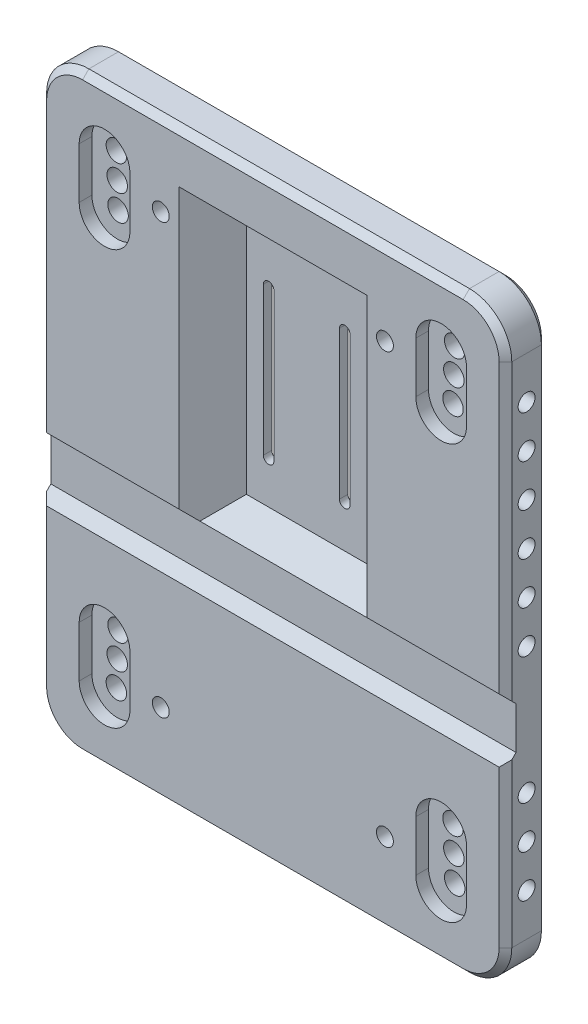
SolidWorks part; units mm, degrees
ref_plane "Front Plane" through (0, 0, 0) normal (0, 0, 1) x (1, 0, 0)
ref_plane "Top Plane" through (0, 0, 0) normal (0, 1, 0) x (1, 0, 0)
ref_plane "Right Plane" through (0, 0, 0) normal (1, 0, 0) x (0, 0, -1)
sketch "Sketch1" plane through (0, 0, 0) normal (0, 0, 1) x (1, 0, 0)
  line L0 (0, 39.3429) -> (0, -40.5174) construction
  line L1 (-55, 70) -> (55, 70)
  line L2 (-55, 70) -> (-55, -70)
  line L3 (-55, -70) -> (55, -70)
  line L4 (55, 70) -> (55, -70)
  line L5 (-55, 70) -> (55, -70) construction
  line L6 (-55, -70) -> (55, 70) construction
  line L7 (-36.7996, 0) -> (34.7101, 0) construction
  line L8 (-9, 40) -> (-9, 5) construction
  line L9 (-7.75, 40) -> (-7.75, 5)
  line L10 (-10.25, 40) -> (-10.25, 5)
  line L11 (9, 40) -> (9, 5) construction
  line L14 (7.75, 40) -> (7.75, 5)
  line L15 (10.25, 40) -> (10.25, 5)
  circle A0 centre (-26.5, 50.75) radius 2
  circle A1 centre (26.5, 50.75) radius 2
  circle A2 centre (26.5, -50.75) radius 2
  circle A3 centre (-26.5, -50.75) radius 2
  circle A4 centre (-40, 55) radius 2.425
  circle A5 centre (40, 55) radius 2.425
  circle A6 centre (40, -55) radius 2.425
  circle A7 centre (-40, -55) radius 2.425
  circle A8 centre (-39.8, 49) radius 2.425
  circle A9 centre (39.8, 49) radius 2.425
  circle A10 centre (39.8, -49) radius 2.425
  circle A11 centre (-39.8, -49) radius 2.425
  circle A12 centre (-39.6, 43.0033) radius 2.425
  circle A13 centre (39.6, 43.0033) radius 2.425
  circle A14 centre (39.6, -43.0033) radius 2.425
  circle A15 centre (-39.6, -43.0033) radius 2.425
  arc A16 (-7.75, 40) -> (-10.25, 40) centre (-9, 40) ccw
  arc A17 (-10.25, 5) -> (-7.75, 5) centre (-9, 5) ccw
  arc A20 (7.75, 40) -> (10.25, 40) centre (9, 40) cw
  arc A21 (10.25, 5) -> (7.75, 5) centre (9, 5) cw
  point P0 (0, 0)
  point P44 (-9, 22.5)
  point P51 (9, 22.5)
  dimension "D3" = 4
  dimension "D4" = 26.5
  dimension "D5" = 50.75
  dimension "D6" = 4.85
  dimension "D7" = 40
  dimension "D8" = 15
  dimension "D9" = 4.85
  dimension "D10" = 39.8
  dimension "D11" = 6
  dimension "D12" = 4.85
  dimension "D13" = 6
  dimension "D14" = 39.6
  dimension "D15" = 1.25
  dimension "D1" = 110
  dimension "D2" = 140
  dimension "D16" = 9
  dimension "D17" = 5
  dimension "D18" = 35
extrude "Boss-Extrude1" add sketch "Sketch1" along normal blind 10
fillet "Fillet1" radius 10 4 edges at (-55, -70, 5) (55, -70, 5) (-55, 70, 5) (55, 70, 5)
sketch "Sketch3" plane through (0, 0, 10) normal (0, 0, 1) x (1, 0, 0)
  line L0 (10.25, 5) -> (10.25, 40) construction
  line L1 (-14.25, 50) -> (14.25, 50)
  line L2 (-14.25, 50) -> (-14.25, -5)
  line L3 (-14.25, -5) -> (14.25, -5)
  line L4 (14.25, 50) -> (14.25, -5)
  line L5 (-14.25, 50) -> (14.25, -5) construction
  line L6 (-14.25, -5) -> (14.25, 50) construction
  arc A0 (-7.75, 40) -> (-10.25, 40) centre (-9, 40) ccw construction
  arc A1 (-10.25, 5) -> (-7.75, 5) centre (-9, 5) ccw construction
  point P0 (0, 22.5)
  dimension "D1" = 10
  dimension "D2" = 10
  dimension "D3" = 4
extrude "Cut-Extrude1" cut sketch "Sketch3" against normal blind 8
chamfer "Chamfer1" distance 8 angle 45 4 edges at (0, -5, 10) (14.25, 22.5, 10) (0, 50, 10) (-14.25, 22.5, 10)
sketch "Sketch5" plane through (-55, 0, 0) normal (-1, 0, 0) x (0, 0, 1)
  line L0 (10, 60) -> (0, 60) construction
  line L1 (10, 60) -> (10, -60) construction
  circle A0 centre (5, 50) radius 2
  circle A1 centre (5, 40) radius 2
  circle A2 centre (5, 30) radius 2
  circle A3 centre (5, 20) radius 2
  circle A4 centre (5, 10) radius 2
  circle A5 centre (5, 0) radius 2
  circle A6 centre (5, -10) radius 2
  circle A7 centre (5, -20) radius 2
  circle A8 centre (5, -30) radius 2
  circle A9 centre (5, -40) radius 2
  circle A10 centre (5, -50) radius 2
  dimension "D1" = 10
  dimension "D2" = 4
  dimension "D3" = 5
  dimension "D4" = 11
extrude "Cut-Extrude3" cut sketch "Sketch5" against normal blind 8
sketch "Sketch6" plane through (55, 0, 0) normal (1, 0, 0) x (0, 0, -1)
  line L0 (0, 60) -> (-10, 60) construction
  line L1 (0, -60) -> (0, 60) construction
  circle A0 centre (-5, 50) radius 2
  circle A1 centre (-5, 40) radius 2
  circle A2 centre (-5, 30) radius 2
  circle A3 centre (-5, 20) radius 2
  circle A4 centre (-5, 10) radius 2
  circle A5 centre (-5, 0) radius 2
  circle A6 centre (-5, -10) radius 2
  circle A7 centre (-5, -20) radius 2
  circle A8 centre (-5, -30) radius 2
  circle A9 centre (-5, -40) radius 2
  circle A10 centre (-5, -50) radius 2
  dimension "D1" = 4
  dimension "D2" = 10
  dimension "D3" = 5
  dimension "D4" = 11
extrude "Cut-Extrude4" cut sketch "Sketch6" against normal blind 8
sketch "Sketch7" plane through (0, 0, 10) normal (0, 0, 1) x (1, 0, 0)
  line L0 (-55, 60) -> (-55, -60) construction
  line L1 (-55, -23) -> (55, -23)
  line L2 (-55, -23) -> (-55, -8)
  line L3 (-55, -8) -> (55, -8)
  line L4 (55, -23) -> (55, -8)
  line L5 (55, -60) -> (55, 60) construction
  line L6 (45, 70) -> (-45, 70) construction
  dimension "D1" = 15
  dimension "D2" = 78
extrude "Cut-Extrude7" cut sketch "Sketch7" against normal blind 2.5
chamfer "Chamfer3" distance 2.5 angle 45 3 edges at (0, -23, 7.5) (-37.375, -8, 7.5) (37.375, -8, 7.5)
chamfer "Chamfer4" distance 1.5 angle 45 18 edges at (-55, 0, 0) (-52.0711, -67.0711, 0) (-52.0711, 67.0711, 0) (0, -70, 0) (0, 70, 0) (52.0711, -67.0711, 0) (52.0711, 67.0711, 0) (55, 0, 0) (55, 26, 10) (-55, 26, 10) (52.0711, 67.0711, 10) (-52.0711, 67.0711, 10) (0, 70, 10) (-55, -41.5, 10) (55, -41.5, 10) (-52.0711, -67.0711, 10) (52.0711, -67.0711, 10) (0, -70, 10)
sketch "Sketch8" plane through (0, 0, 10) normal (0, 0, -1) x (-1, 0, 0)
  line L0 (-39.8, 43) -> (-39.8, 55) construction
  line L1 (-45.8, 43) -> (-45.8, 55)
  line L2 (-33.8, 43) -> (-33.8, 55)
  line L3 (0, 50.6508) -> (0, -40.492) construction
  line L4 (-37.1333, 0) -> (41.9805, 0) construction
  line L5 (39.8, 43) -> (39.8, 55) construction
  line L6 (45.8, 43) -> (45.8, 55)
  line L7 (33.8, 43) -> (33.8, 55)
  line L8 (39.8, -43) -> (39.8, -55) construction
  line L9 (45.8, -43) -> (45.8, -55)
  line L10 (33.8, -43) -> (33.8, -55)
  line L11 (-39.8, -43) -> (-39.8, -55) construction
  line L12 (-45.8, -43) -> (-45.8, -55)
  line L13 (-33.8, -43) -> (-33.8, -55)
  arc A0 (-45.8, 43) -> (-33.8, 43) centre (-39.8, 43) ccw
  arc A1 (-33.8, 55) -> (-45.8, 55) centre (-39.8, 55) ccw
  circle A2 centre (-39.8, 49) radius 2.425 construction
  arc A3 (45.8, 43) -> (33.8, 43) centre (39.8, 43) cw
  arc A4 (33.8, 55) -> (45.8, 55) centre (39.8, 55) cw
  arc A5 (45.8, -43) -> (33.8, -43) centre (39.8, -43) ccw
  arc A6 (33.8, -55) -> (45.8, -55) centre (39.8, -55) ccw
  arc A7 (-45.8, -43) -> (-33.8, -43) centre (-39.8, -43) cw
  arc A8 (-33.8, -55) -> (-45.8, -55) centre (-39.8, -55) cw
  point P2 (-39.8, 49)
  point P7 (-39.6, 43.0033)
  point P10 (-40, 55)
  point P20 (39.8, 49)
  point P27 (39.8, -49)
  point P34 (-39.8, -49)
  dimension "D1" = 6
extrude "Cut-Extrude8" cut sketch "Sketch8" along normal blind 3
sketch "Sketch9" plane through (55, 0, 0) normal (1, 0, 0) x (0, 0, -1)
  line L0 (-7.4795, -9.1307) -> (-5.6879, -6.8273)
  line L1 (-5.6879, -6.8273) -> (-2.4538, -7.5718)
  line L2 (-2.4538, -7.5718) -> (-2.4538, -22.4394)
  line L3 (-2.4538, -22.4394) -> (-6.4325, -22.4394)
  line L4 (-6.4325, -22.4394) -> (-7.1506, -20.5769)
  line L5 (-7.1506, -20.5769) -> (-7.1506, -10.5035)
  line L6 (-7.1506, -10.5035) -> (-7.4795, -9.1307)
extrude "Boss-Extrude3" add sketch "Sketch9" against normal blind 10
sketch "Sketch10" plane through (0, 0, 0) normal (0, 0, -1) x (-1, 0, 0)
  line L0 (0, 41.7558) -> (0, -38.9553) construction
  line L1 (-29.95, 54.2) -> (-23.05, 54.2)
  line L2 (-29.95, 54.2) -> (-29.95, 47.3)
  line L3 (-29.95, 47.3) -> (-23.05, 47.3)
  line L4 (-23.05, 54.2) -> (-23.05, 47.3)
  line L5 (-29.95, 54.2) -> (-23.05, 47.3) construction
  line L6 (-29.95, 47.3) -> (-23.05, 54.2) construction
  line L7 (0, -38.9553) -> (0, 0) construction
  line L8 (0, 0) -> (24.8367, 0) construction
  line L9 (29.95, 47.3) -> (23.05, 47.3)
  line L10 (23.05, 54.2) -> (23.05, 47.3)
  line L11 (29.95, 54.2) -> (23.05, 54.2)
  line L12 (29.95, 54.2) -> (29.95, 47.3)
  line L13 (29.95, -54.2) -> (29.95, -47.3)
  line L14 (29.95, -54.2) -> (23.05, -54.2)
  line L15 (23.05, -54.2) -> (23.05, -47.3)
  line L16 (29.95, -47.3) -> (23.05, -47.3)
  line L17 (-29.95, -47.3) -> (-23.05, -47.3)
  line L18 (-23.05, -54.2) -> (-23.05, -47.3)
  line L19 (-29.95, -54.2) -> (-23.05, -54.2)
  line L20 (-29.95, -54.2) -> (-29.95, -47.3)
  point P0 (-26.5, 50.75)
  dimension "D1" = 6.9
  dimension "D2" = 6.9
extrude "Cut-Extrude9" cut sketch "Sketch10" against normal blind 5
sketch "Sketch11" plane through (-55, 0, 0) normal (-1, 0, 0) x (0, 0, 1)
  line L0 (2.4601, -8.6141) -> (4.3527, -6.8954)
  line L1 (4.3527, -6.8954) -> (7.1335, -6.8954)
  line L2 (7.1335, -6.8954) -> (7.9253, -8.9617)
  line L3 (7.9253, -8.9617) -> (7.1335, -10.6225)
  line L4 (7.1335, -10.6225) -> (7.1335, -21.3984)
  line L5 (7.1335, -21.3984) -> (5, -22.866)
  line L6 (5, -22.866) -> (2.7112, -22.615)
  line L7 (2.7112, -22.615) -> (2.267, -15.0449)
  line L8 (2.267, -15.0449) -> (2.4601, -8.6141)
extrude "Boss-Extrude4" add sketch "Sketch11" against normal blind 10
